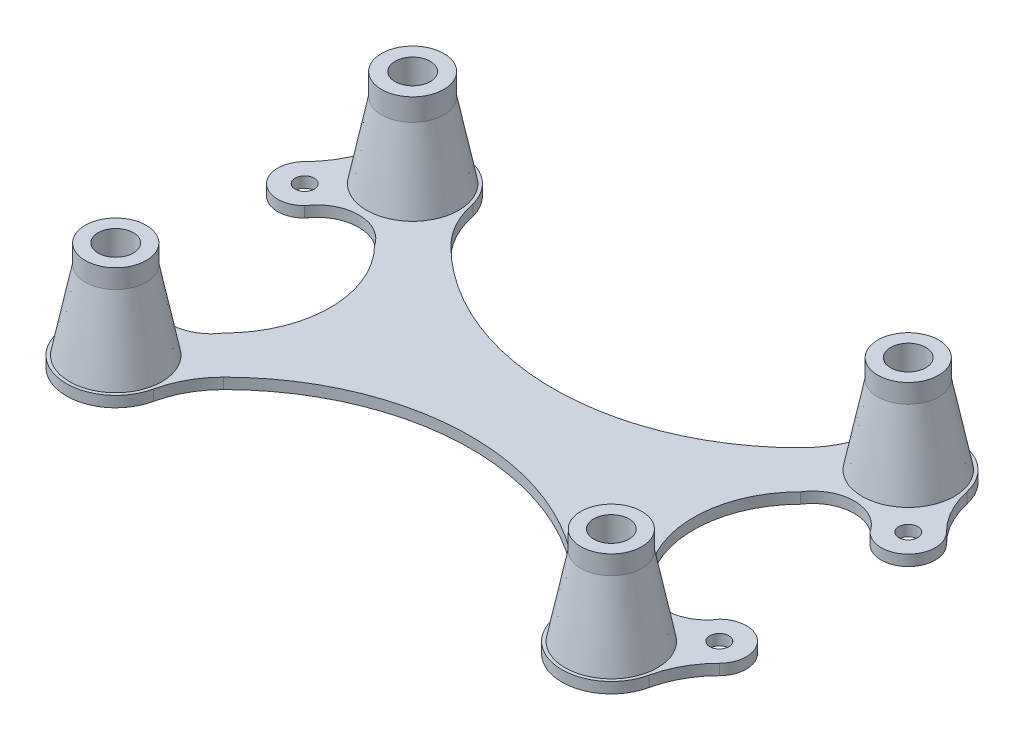
SolidWorks part; units mm, degrees
material "ABS"
ref_plane "Front Plane" through (0, 0, 0) normal (0, 0, 1) x (1, 0, 0)
ref_plane "Top Plane" through (0, 0, 0) normal (0, 1, 0) x (1, 0, 0)
ref_plane "Right Plane" through (0, 0, 0) normal (1, 0, 0) x (0, 0, -1)
sketch "Sketch1" plane through (0, 0, 0) normal (0, 1, 0) x (1, 0, 0)
  line L0 (-17.1901, 8.2099) -> (-8.2099, 17.1901) construction
  line L1 (-12.7, -12.7) -> (12.7, -12.7) construction
  line L2 (-12.7, -12.7) -> (-12.7, 12.7) construction
  line L3 (-12.7, 12.7) -> (12.7, 12.7) construction
  line L4 (12.7, -12.7) -> (12.7, 12.7) construction
  line L5 (-12.7, -12.7) -> (12.7, 12.7) construction
  line L6 (-12.7, 12.7) -> (12.7, -12.7) construction
  line L7 (8.2099, 17.1901) -> (17.1901, 8.2099) construction
  line L8 (-17.1901, -8.2099) -> (-8.2099, -17.1901) construction
  line L9 (8.2099, -17.1901) -> (17.1901, -8.2099) construction
  line L10 (99.3959, 8.2099) -> (108.3761, 17.1901) construction
  line L11 (103.886, -12.7) -> (129.286, -12.7) construction
  line L12 (103.886, -12.7) -> (103.886, 12.7) construction
  line L13 (103.886, 12.7) -> (129.286, 12.7) construction
  line L14 (129.286, -12.7) -> (129.286, 12.7) construction
  line L15 (103.886, -12.7) -> (129.286, 12.7) construction
  line L16 (103.886, 12.7) -> (129.286, -12.7) construction
  line L17 (124.7959, 17.1901) -> (133.7761, 8.2099) construction
  line L18 (99.3959, -8.2099) -> (108.3761, -17.1901) construction
  line L19 (124.7959, -17.1901) -> (133.7761, -8.2099) construction
  line L20 (-17.1901, -61.6401) -> (-8.2099, -52.6599) construction
  line L21 (-12.7, -82.55) -> (12.7, -82.55) construction
  line L22 (-12.7, -82.55) -> (-12.7, -57.15) construction
  line L23 (-12.7, -57.15) -> (12.7, -57.15) construction
  line L24 (12.7, -82.55) -> (12.7, -57.15) construction
  line L25 (-12.7, -82.55) -> (12.7, -57.15) construction
  line L26 (-12.7, -57.15) -> (12.7, -82.55) construction
  line L27 (8.2099, -52.6599) -> (17.1901, -61.6401) construction
  line L28 (-17.1901, -78.0599) -> (-8.2099, -87.0401) construction
  line L29 (8.2099, -87.0401) -> (17.1901, -78.0599) construction
  line L30 (99.3959, -61.6401) -> (108.3761, -52.6599) construction
  line L31 (103.886, -82.55) -> (129.286, -82.55) construction
  line L32 (103.886, -82.55) -> (103.886, -57.15) construction
  line L33 (103.886, -57.15) -> (129.286, -57.15) construction
  line L34 (129.286, -82.55) -> (129.286, -57.15) construction
  line L35 (103.886, -82.55) -> (129.286, -57.15) construction
  line L36 (103.886, -57.15) -> (129.286, -82.55) construction
  line L37 (124.7959, -52.6599) -> (133.7761, -61.6401) construction
  line L38 (99.3959, -78.0599) -> (108.3761, -87.0401) construction
  line L39 (124.7959, -87.0401) -> (133.7761, -78.0599) construction
  line L40 (12.7, -12.7) -> (103.886, -57.15) construction
  line L41 (12.7, -57.15) -> (103.886, -12.7) construction
  circle A2 centre (12.7, -12.7) radius 6.35
  circle A3 centre (-12.7, -12.7) radius 6.35
  circle A4 centre (0, 0) radius 7.325
  circle A5 centre (0, 0) radius 4.15
  circle A6 centre (0, -69.85) radius 11.6105
  circle A7 centre (116.586, -69.85) radius 11.6105
  arc A8 (-8.2099, -17.1901) -> (8.2099, -17.1901) centre (0, -22.4506) cw
  circle A9 centre (116.586, 0) radius 11.6105
  circle A12 centre (129.286, -12.7) radius 6.35
  circle A13 centre (103.886, -12.7) radius 6.35
  circle A14 centre (116.586, 0) radius 7.175
  circle A15 centre (116.586, 0) radius 4.15
  circle A16 centre (0, 0) radius 11.6105
  arc A17 (-17.1901, -8.2099) -> (-11.3418, 2.4833) centre (-32.5204, 7.1204) ccw
  arc A18 (108.3761, -17.1901) -> (124.7959, -17.1901) centre (116.586, -22.4506) cw
  arc A19 (17.1901, -8.2099) -> (11.2299, 2.9483) centre (32.5835, 7.1835) cw
  circle A20 centre (-12.7, -57.15) radius 6.35
  circle A21 centre (12.7, -57.15) radius 6.35
  circle A24 centre (0, -69.85) radius 7.175
  circle A25 centre (0, -69.85) radius 4.15
  arc A26 (-8.2099, -52.6599) -> (8.2099, -52.6599) centre (0, -47.3994) ccw
  arc A27 (99.3959, -8.2099) -> (105.3561, 2.9483) centre (84.0025, 7.1835) ccw
  arc A28 (133.7761, -8.2099) -> (127.9278, 2.4833) centre (149.1064, 7.1204) cw
  arc A29 (133.7761, -61.6401) -> (127.9278, -72.3333) centre (149.1064, -76.9704) ccw
  circle A30 centre (103.886, -57.15) radius 6.35
  circle A31 centre (129.286, -57.15) radius 6.35
  circle A34 centre (116.586, -69.85) radius 7.175
  circle A35 centre (116.586, -69.85) radius 4.15
  arc A36 (108.3761, -52.6599) -> (124.7959, -52.6599) centre (116.586, -47.3994) ccw
  arc A37 (99.3959, -61.6401) -> (105.2442, -72.3333) centre (84.0656, -76.9704) cw
  arc A38 (17.1901, -61.6401) -> (11.3418, -72.3333) centre (32.5204, -76.9704) ccw
  arc A39 (-17.1901, -61.6401) -> (-11.3418, -72.3333) centre (-32.5204, -76.9704) cw
  arc A40 (8.2099, -17.1901) -> (8.2099, -52.6599) centre (-9.525, -34.925) cw
  arc A41 (17.1901, -8.2099) -> (99.3959, -8.2099) centre (58.293, 32.893) ccw
  arc A42 (108.3761, -17.1901) -> (108.3761, -52.6599) centre (126.111, -34.925) ccw
  arc A43 (99.3959, -61.6401) -> (17.1901, -61.6401) centre (58.293, -102.743) ccw
  point P0 (0, 0)
  point P16 (-12.7, 12.7)
  point P19 (12.7, 12.7)
  point P22 (-12.7, -12.7)
  point P25 (12.7, -12.7)
  point P29 (116.586, 0)
  point P44 (103.886, 12.7)
  point P47 (129.286, 12.7)
  point P50 (103.886, -12.7)
  point P53 (129.286, -12.7)
  point P57 (0, -69.85)
  point P72 (-12.7, -57.15)
  point P75 (12.7, -57.15)
  point P78 (-12.7, -82.55)
  point P81 (12.7, -82.55)
  point P85 (116.586, -69.85)
  point P100 (103.886, -57.15)
  point P103 (129.286, -57.15)
  point P106 (103.886, -82.55)
  point P109 (129.286, -82.55)
  dimension "D1" = 8.3
  dimension "D3" = 3.175
  dimension "D5" = 8.3
  dimension "D6" = 12.7
  dimension "D9" = 8.3
  dimension "D10" = 12.7
  dimension "D13" = 8.3
  dimension "D14" = 12.7
  dimension "D15" = 14.35
  dimension "D17" = 14.35
  dimension "D18" = 14.35
  dimension "D19" = 25.0809
  dimension "D20" = 25.0809
  dimension "D21" = 58.1282
  dimension "D22" = 58.1282
  dimension "D23" = 12.7
  dimension "D4" = 25.4
  dimension "D7" = 69.85
  dimension "D8" = 25.4
  dimension "D11" = 116.586
  dimension "D12" = 25.4
  dimension "D16" = 25.4
extrude "Boss-Extrude1" add sketch "Sketch1" along normal blind 2.54 contours A3 A8 | A2 A6 A7 A3 A8 A4 | A2 A8 | A6 | A4 A5 | A5 | A7 | A43 A30 A42 A13 A41 A2 A40 A21 | A20 A26 | A21 A26 A20 A24 | A24 A25 | A21 A26 | A30 A36 | A31 A36 A30 A34 | A31 A36 | A13 A18 | A12 A13 A18 A14 | A34 A35 | A25 | A35 | A14 A15 | A15 | A12 A18 | A16 A19 A4 | A17 A3 A16 | A2 A19 A16 | A27 A9 A14 | A12 A28 A9 | A27 A13 A9 | A30 A37 A7 | A31 A7 A29 | A20 A39 A6 | A38 A21 A6 region at (12.7039, 0, 12.697) region at (58.293, 0, 34.925) region at (12.4175, 0, 4.4713) region at (0, 0, 12.1896) region at (0, 0, 11.2821) region at (103.8821, 0, 12.697) region at (104.1685, 0, 4.4713) region at (12.7039, 0, 57.153) region at (-12.7039, 0, 12.697) region at (-12.4175, 0, 4.4601) region at (105.8215, 0, 3.378) region at (116.586, 0, 12.1896) region at (0, 0, 57.6604) region at (103.8821, 0, 57.153) region at (129.0035, 0, 4.4601) region at (129.2899, 0, 12.697) region at (12.4175, 0, 65.3899) region at (10.4233, 0, 65.5325) region at (-12.7039, 0, 57.153) region at (104.1685, 0, 65.3899) region at (116.586, 0, 57.6604) region at (-12.4175, 0, 65.3899) region at (116.586, 0, 58.5679) region at (129.2899, 0, 57.153) region at (129.0035, 0, 65.3899) region at (-7.1178, 0, 0) region at (0, 0, 0) region at (109.6139, 0, 0) region at (116.586, 0, 0) region at (-6.9721, 0, 69.85) region at (0, 0, 69.85) region at (109.6139, 0, 69.85) region at (116.586, 0, 69.85)
extrude "Boss-Extrude2" add sketch "Sketch1<4>" along normal blind 25.4 contours A4 A5 | A14 A15 | A24 A25 | A34 A35 region at (-7.1178, 0, 0) region at (109.6139, 0, 0) region at (-6.9721, 0, 69.85) region at (109.6139, 0, 69.85)
sketch "Sketch1<4>" plane through (0, 0, 0) normal (0, 1, 0) x (1, 0, 0) same geometry as "Sketch1"
hole_wizard "#8 Clearance Hole2" positions "Sketch6" profile "Sketch7" hole size "#8" standard "ANSI Inch" end condition through all
sketch "Sketch6" plane through (0, 2.54, 0) normal (0, 1, 0) x (1, 0, 0)
  point P6 (129.286, -12.7)
  point P9 (129.286, -57.15)
  point P24 (-12.7, -57.15)
  point P28 (-12.7, -12.7)
sketch "Sketch7" plane through (129.286, 2.54, 12.7) normal (1, 0, 0) x (0, 0, 1)
  line L0 (0, 0) -> (0, 2.54)
  line L1 (0, 2.54) -> (2.2479, 2.54)
  line L2 (2.2479, 2.54) -> (2.2479, 0)
  line L5 (2.2479, 0) -> (0, 0)
  line L11 (0, -6.35) -> (0, 107.95) construction
  dimension "Thru Hole Dia." = 4.4958
  dimension "Thru Hole Depth" = 2.54
sketch "Sketch8" plane through (0, 0, 0) normal (1, 0, 0) x (0, 0, -1)
  line L0 (10.8569, 2.54) -> (7.0469, 21.59)
  line L1 (11.6105, 2.54) -> (2.4833, 2.54) construction
  line L2 (7.0469, 21.59) -> (7.0469, 2.54)
  line L3 (7.0469, 2.54) -> (10.8569, 2.54)
  line L4 (0, 0) -> (0, 30.7064) construction
  dimension "D1" = 19.05
  dimension "D2" = 3.81
revolve "Revolve1" add sketch "Sketch8" angle 360 about L4
sketch "Sketch9" plane through (0, 0, 0) normal (0, 1, 0) x (1, 0, 0)
  line L0 (-8.2742, -34.6778) -> (140.5133, -34.6778) construction
  line L1 (66.1196, -79.6601) -> (66.1196, 9.6453) construction
pattern_linear "LPattern1" count 2 spacing 116.586 along (1, 0, 0) count 2 spacing 69.85 along (0, 0, 1) of "Revolve1"
